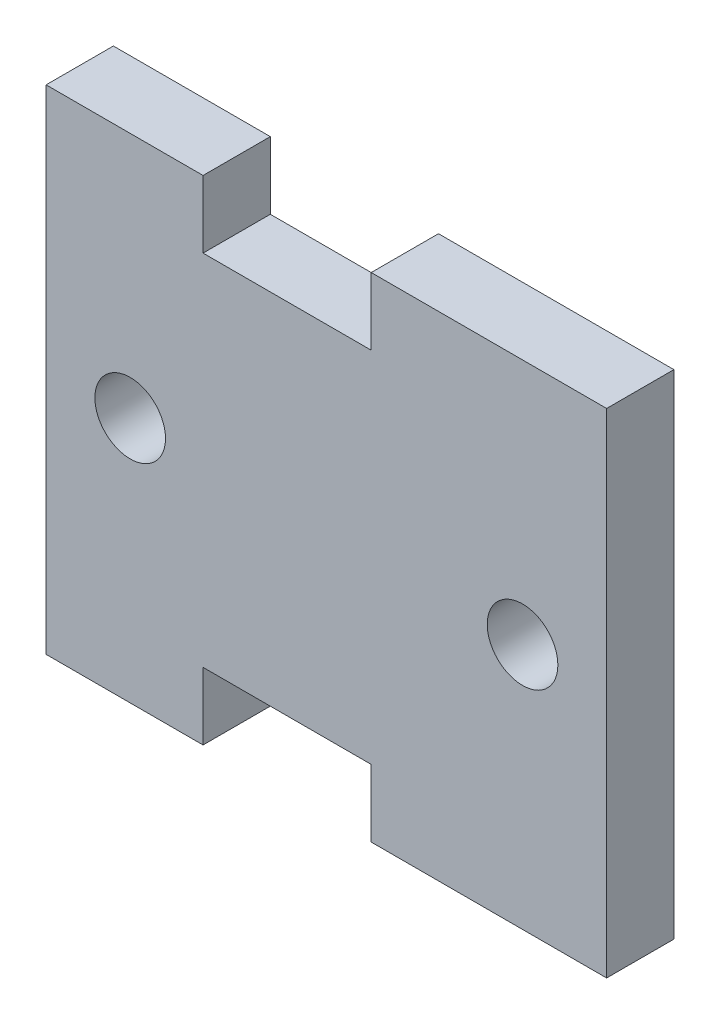
SolidWorks part; units mm, degrees
ref_plane "Plano frontal" through (0, 0, 0) normal (0, 0, 1) x (1, 0, 0)
ref_plane "Plano superior" through (0, 0, 0) normal (0, 1, 0) x (1, 0, 0)
ref_plane "Plano direito" through (0, 0, 0) normal (1, 0, 0) x (0, 0, -1)
sketch "Esboço1" plane through (0, 0, 0) normal (0, 0, 1) x (1, 0, 0)
  line L0 (-17.5, 0) -> (17.5, 0) construction
  line L1 (-25, -22) -> (25, -22)
  line L2 (-25, -22) -> (-25, 22)
  line L3 (-25, 22) -> (25, 22)
  line L4 (25, -22) -> (25, 22)
  line L5 (-25, -22) -> (25, 22) construction
  line L6 (-25, 22) -> (25, -22) construction
  line L7 (4, 16) -> (-11, 16)
  line L8 (4, 16) -> (4, 22)
  line L9 (4, 22) -> (-11, 22)
  line L10 (-11, 16) -> (-11, 22)
  line L11 (4, 16) -> (-11, 22) construction
  line L12 (4, 22) -> (-11, 16) construction
  line L13 (4, -22) -> (-11, -22)
  line L14 (-11, -16) -> (-11, -22)
  line L15 (4, -16) -> (-11, -16)
  line L16 (4, -16) -> (4, -22)
  circle A0 centre (-17.5, 0) radius 3.15
  circle A1 centre (17.5, 0) radius 3.15
  point P0 (0, 0)
  point P6 (0, 20.4)
  point P13 (0, 0)
  point P14 (-24.1449, -22)
  point P15 (-11.0908, 16)
  point P28 (25, 0)
  dimension "D5" = 6.3
  dimension "D1" = 44
  dimension "D2" = 15
  dimension "D3" = 35
  dimension "D4" = 6
  dimension "D6" = 7.5
  dimension "D7" = 7.5
  dimension "D8" = 14
extrude "Ressalto-extrusão1" add sketch "Esboço1" along normal blind 6 contours L15 L16 L1 L4 L3 L8 L7 L10 L2 L14 A0 region at (0.3218, 0, 0)
